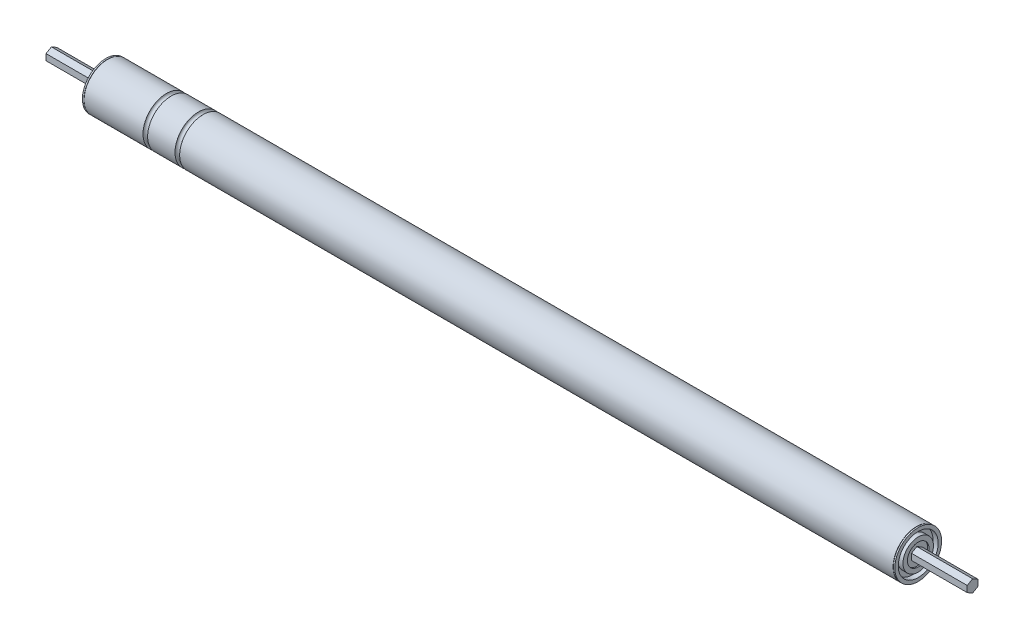
SolidWorks part; units mm, degrees
ref_plane "Front Plane" through (0, 0, 0) normal (0, 0, 1) x (1, 0, 0)
ref_plane "Top Plane" through (0, 0, 0) normal (0, 1, 0) x (1, 0, 0)
ref_plane "Right Plane" through (0, 0, 0) normal (1, 0, 0) x (0, 0, -1)
sketch "Sketch1" plane through (0, 0, 0) normal (0, 0, 1) x (1, 0, 0)
  line L0 (-417.5125, 0) -> (417.5125, 0) construction
  line L1 (417.5125, 0) -> (431.8, 0) construction
  line L2 (-417.5125, 0) -> (-431.8, 0) construction
  line L3 (0, 24.13) -> (0, -24.13) construction
  line L4 (-431.8, 5.5562) -> (-431.8, -5.5563) construction
  line L5 (431.8, 5.5562) -> (431.8, -5.5562) construction
  line L6 (-418.8969, 24.13) -> (-418.8969, -24.13) construction
  line L7 (-418.8969, 0) -> (418.8969, 0) construction
  line L8 (418.8969, 24.13) -> (418.8969, -24.13) construction
  line L9 (-354.0125, 24.13) -> (-354.0125, -24.13) construction
  line L10 (-356.3938, 21.7188) -> (-351.6313, 21.7188) construction
  line L11 (-419.1, 11.1125) -> (-419.1, -11.1125) construction
  line L12 (419.1, 11.1125) -> (419.1, -11.1125) construction
  point P2 (-419.1, 0)
  point P6 (419.1, 0)
  point P23 (-354.0125, 21.7188)
  dimension "D1" = 1.5875
  dimension "D2" = 1.5875
  dimension "BF" = 838.2
  dimension "Overall Width" = 863.6
  dimension "D4" = 48.26
  dimension "D5" = 11.1125
  dimension "D6" = 837.7937
  dimension "D8" = 2.4112
  dimension "D9" = 4.7625
  dimension "D10" = 22.225
  dimension "Bearing to Groove Width" = 63.5
sketch "Sketch2" plane through (0, 0, 0) normal (0, 0, 1) x (1, 0, 0)
  line L0 (-417.5125, 0) -> (-417.5125, 11.1125)
  line L1 (-417.5125, 11.1125) -> (-418.8969, 11.1125)
  line L2 (-418.8969, 24.13) -> (-418.8969, -24.13) construction
  line L3 (-417.5125, 0) -> (-431.8, 0) construction
  line L4 (-418.8969, 11.1125) -> (-418.8969, 15.7129)
  line L5 (-417.5125, 0) -> (-411.7849, 0) construction
  line L6 (-417.5125, 0) -> (-411.7849, 0)
  line L7 (-418.8969, 15.7129) -> (-413.5629, 15.7129)
  line L8 (-413.5629, 15.7129) -> (-413.5629, 20.574)
  line L9 (-418.8969, 24.13) -> (-418.8969, 20.574)
  line L10 (-418.8969, 20.574) -> (-413.5629, 20.574)
  line L11 (-418.8969, 24.13) -> (-417.1189, 24.13)
  line L12 (-417.1189, 24.13) -> (-417.1189, 22.352)
  line L13 (-417.1189, 22.352) -> (-411.7849, 22.352)
  line L14 (-411.7849, 22.352) -> (-411.7849, 0)
  line L15 (-417.5125, 0) -> (417.5125, 0) construction
  line L16 (-431.8, 5.5562) -> (-431.8, -5.5563) construction
  dimension "D3" = 22.225
  dimension "D1" = 1.778
  dimension "D2" = 1.778
  dimension "D4" = 1.778
  dimension "D5" = 31.4259
  dimension "D6" = 1.778
  dimension "D7" = 5.334
revolve "Revolve1" add sketch "Sketch2" angle 360 mid plane about L5
mirror "Mirror2" about plane through (0, 0, 0) normal (1, 0, 0) of bodies 101
sketch "Sketch3" plane through (0, 0, 0) normal (1, 0, 0) x (0, 0, -1)
  circle A0 centre (0, 0) radius 24.13
  circle A1 centre (0, 0) radius 22.352 construction
  circle A2 centre (0, 0) radius 22.352 construction
extrude "Boss-Extrude1" add sketch "Sketch3" along normal up to surface (411.7849 mm away) and the other way up to surface (411.7849 mm away) up to face at (411.7849, -22.352, 0) other way up to face at (-411.7849, -22.352, 0)
chamfer "Chamfer1" distance 0.254 angle 45 2 edges at (-417.1189, -24.13, 0) (417.1189, -24.13, 0)
sketch "Sketch6" plane through (-411.7849, 0, 0) normal (-1, 0, 0) x (0, 0, 1)
  circle A0 centre (0, 0) radius 22.352 construction
  circle A1 centre (0, 0) radius 24.13
  circle A2 centre (0, 0) radius 24.13
  circle A3 centre (0, 0) radius 22.352
  dimension "D1" = 0
extrude "Boss-Extrude3" add sketch "Sketch6" along normal up to surface and the other way up to surface up to face at (-417.1189, -23.876, 0) other way up to face at (417.1189, 23.876, 0)
sketch "Sketch4" plane through (0, 0, 0) normal (1, 0, 0) x (0, 0, -1)
  line L1 (0, 6.4158) -> (-5.5563, 3.2079)
  line L2 (-5.5563, 3.2079) -> (-5.5563, -3.2079)
  line L3 (-5.5563, -3.2079) -> (0, -6.4158)
  line L4 (0, -6.4158) -> (5.5562, -3.2079)
  line L5 (5.5562, -3.2079) -> (5.5562, 3.2079)
  line L6 (5.5562, 3.2079) -> (0, 6.4158)
  circle A0 centre (0, 0) radius 5.5563 construction
  dimension "D1" = 11.1125
extrude "Boss-Extrude2" add sketch "Sketch4" along normal up to vertex and the other way up to vertex up to point (431.8, 0, 0) other way up to point (-431.8, 0, 0)
sketch "Sketch5" plane through (0, 0, 0) normal (0, 0, 1) x (1, 0, 0)
  line L0 (-356.3938, 21.7188) -> (-351.6313, 21.7188) construction
  line L1 (-354.0125, 24.13) -> (-354.0125, -24.13) construction
  line L2 (-356.3938, 21.7188) -> (-356.3938, 25.5224) construction
  line L3 (-431.8, 0) -> (-417.5125, 0) construction
  line L7 (-354.0125, 24.1) -> (-356.3938, 24.1) construction
  line L8 (-357.1811, 24.8874) -> (-357.1811, 25.5224)
  line L9 (-357.1811, 25.5224) -> (-350.8438, 25.5224)
  line L10 (-350.8438, 24.8874) -> (-350.8438, 25.5224)
  arc A0 (-356.3938, 24.1) -> (-351.6312, 24.1) centre (-354.0125, 24.1) ccw
  arc A1 (-351.6312, 24.1) -> (-350.8438, 24.8874) centre (-350.8438, 24.1) cw
  arc A2 (-356.3938, 24.1) -> (-357.1811, 24.8874) centre (-357.1811, 24.1) ccw
  dimension "D2" = 0.7874
  dimension "D1" = 0.03
  dimension "D3" = 0.635
revolve "Cut-Revolve1" cut sketch "Sketch5" angle 360 mid plane about L3
pattern_linear "LPattern1" count 2 spacing 33.02 along (1, 0, 0) of "Cut-Revolve1"
ref_axis "Center Axis 1" through (307.34, 0, 0) along (-1, 0, 0)
ref_plane "Contact Plane 1" through (-431.8, 0, 0) normal (-1, 0, 0) x (0, 0, 1)
ref_plane "Contact Plane 2" through (-417.5125, 0, 0) normal (-1, 0, 0) x (0, 0, 1)
extrude "Boss-Extrude4" add sketch "Sketch4<3>" along normal blind 475
sketch "Sketch4<3>" plane through (0, 0, 0) normal (1, 0, 0) x (0, 0, -1) same geometry as "Sketch4"
extrude "Boss-Extrude5" add sketch "Sketch4<4>" against normal blind 475
sketch "Sketch4<4>" plane through (0, 0, 0) normal (1, 0, 0) x (0, 0, -1) same geometry as "Sketch4"
equation "\"D6@Sketch1\" = \"BF@Sketch1\"-.40625"
equation "\"D3@Sketch2\" = \"D5@Sketch1\"*2"
equation "\"D10@Sketch1\" = \"D3@Sketch2\""
equation "\"D2@Sketch2\" = \"D1@Sketch2\""
equation "\"D4@Sketch2\" = \"D2@Sketch2\""
equation "\"D6@Sketch2\" = \"D1@Sketch2\""
equation "\"D7@Sketch2\" = \"D1@Sketch2\"*3"
equation "\"D8@Sketch1\"=(\"D9@Sketch1\"/2)+.030"
